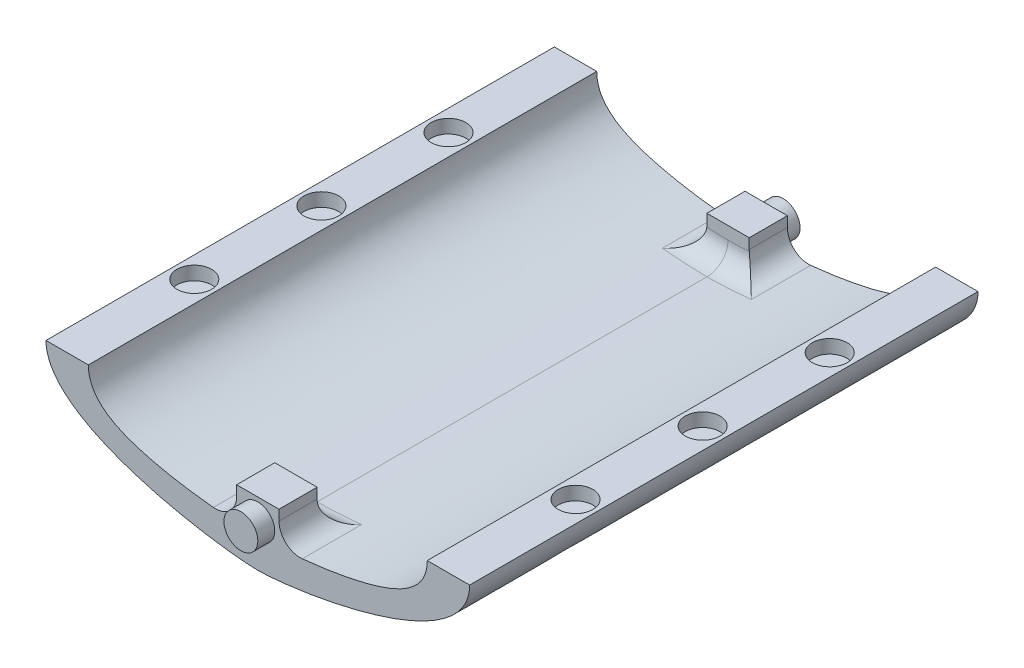
SolidWorks part; units mm, degrees
material "ASA-AERO"
ref_plane "Front Plane" through (0, 0, 0) normal (0, 0, 1) x (1, 0, 0)
ref_plane "Top Plane" through (0, 0, 0) normal (0, 1, 0) x (1, 0, 0)
ref_plane "Right Plane" through (0, 0, 0) normal (1, 0, 0) x (0, 0, -1)
sketch "Sketch2" plane through (0, 0, 0) normal (0, 0, 1) x (1, 0, 0)
  line L0 (0, 0) -> (0, 60.3008) construction
  line L1 (50, 0) -> (50, 60.3008) construction
  line L2 (0, 0) -> (25, 0) construction
  line L3 (0, -12) -> (0, -5)
  line L4 (25, -5) -> (25, -8) construction
  line L7 (25, 0) -> (25, -8) construction
  line L8 (50, 0) -> (50, 10) construction
  line L9 (50, 0) -> (112.8617, 0) construction
  line L10 (50, 10) -> (40, 10)
  line L11 (40, 10) -> (40, 19.3377) construction
  line L12 (25, 0) -> (25, -2) construction
  spline S0 degree 3 poles (0, -5) (3.5888, -5) (23.3364, -4.1199) (40, 2.9806) (40, 10) knots 0 0 0 0 0.567247 1 1 1 1
  spline S1 degree 3 poles (0, -12) (8.9645, -12) (50, -6.0901) (50, 10) knots 0 0 0 0 1 1 1 1
  point P4 (0, 0)
  point P8 (50, 0)
  dimension "D6" = 7
  dimension "D9" = 10
  dimension "D7" = 2
  dimension "D1" = 50
  dimension "D2" = 12
  dimension "D3" = 8
  dimension "D4" = 25
  dimension "D5" = 10
  dimension "D8" = 5
ref_plane "Plane1" through (0, 0, -30) normal (0, 0, 1) x (1, 0, 0)
sketch "Sketch3" plane through (0, 0, -30) normal (0, 0, 1) x (1, 0, 0)
  line L0 (0, 0) -> (0, 5) construction
  line L1 (0, 5) -> (30, 5) construction
  line L3 (0, 0) -> (0, -10) construction
  line L4 (0, -10) -> (0, -5)
  line L6 (15, 5) -> (15, -0.5) construction
  line L7 (15, -0.5) -> (15, -6) construction
  line L8 (30, 10) -> (30, 17.2192) construction
  line L9 (0, 5) -> (30, 5) construction
  line L10 (30, 10) -> (25.3573, 10)
  line L11 (30, 5) -> (30, 10) construction
  line L12 (25.3573, 10) -> (25.3573, 15.9682) construction
  spline S0 degree 3 poles (0, -5) (3.0165, -5) (13.9916, -1.9794) (25.3573, 5.259) (25.3573, 10) knots 0 0 0 0 0.540738 1 1 1 1
  spline S1 degree 3 poles (0, -10) (3.3297, -10) (17.9348, -6.1582) (30, 2.4303) (30, 10) knots 0 0 0 0 0.414466 1 1 1 1
  dimension "D1" = 5
  dimension "D2" = 30
  dimension "D3" = 5
  dimension "D4" = 10
  dimension "D5" = 5.5
  dimension "D6" = 5.5
ref_plane "Plane2" through (0, 0, -60) normal (0, 0, 1) x (1, 0, 0)
sketch "Sketch5" plane through (0, 0, -60) normal (0, 0, 1) x (1, 0, 0)
  line L0 (0, 0) -> (0, 10) construction
  line L1 (0, 10) -> (10, 10) construction
  line L2 (5, 10) -> (10, 10)
  line L3 (0, 0) -> (0, 5)
  line L4 (5, 10) -> (5, 13.8122) construction
  line L5 (10, 10) -> (10, 16.2533) construction
  line L6 (0, 0) -> (-6.3495, 0) construction
  line L7 (0, 5) -> (-5.8986, 5) construction
  spline S0 degree 3 poles (0, 5) (0.922, 5) (4.0789, 6.1641) (5, 8.7602) (5, 10) knots 0 0 0 0 0.511134 1 1 1 1
  spline S1 degree 3 poles (0, 0) (3.3679, 0) (8.0705, 2.1657) (10, 7.206) (10, 10) knots 0 0 0 0 0.525707 1 1 1 1
  dimension "D1" = 10
  dimension "D2" = 10
sketch "Sketch6" plane through (0, 0, 0) normal (1, 0, 0) x (0, 0, -1)
  spline S1 degree 2 poles (60, 0) (31.5145, -13.7022) (0, -12) knots 0 0 0 1 1 1
sketch "Sketch8" plane through (0, 0, 0) normal (1, 0, 0) x (0, 0, -1)
  spline S0 degree 2 poles (60, 5) (31.5811, -9.7434) (0, -5) knots 0 0 0 1 1 1
sketch3d "3DSketch3"
  spline S0 degree 2 poles (5, 10, -60) (26.7783, 10, -32.4788) (40, 10, 0) knots 0 0 0 1 1 1
  spline S1 degree 2 poles (10, 10, -60) (30, 10, -30) (50, 10, 0) knots 0 0 0 1 1 1
extrude "Boss-Extrude3" add sketch "Sketch2<6>" along normal blind 120 contours S0 L10 S1 L3
sketch "Sketch2<6>" plane through (0, 0, 0) normal (0, 0, 1) x (1, 0, 0) same geometry as "Sketch2"
mirror "Mirror3" about plane through (0, 0, 0) normal (1, 0, 0) of "Boss-Extrude3"
loft "Loft3" [suppressed] add profiles "Sketch2", "Sketch3", "Sketch5"
mirror "Mirror1" [suppressed] about plane through (0, 0, 0) normal (1, 0, 0) of bodies 103
sketch "Sketch11" [suppressed] plane through (0, 10, 0) normal (0, 1, 0) x (1, 0, 0)
  line L0 (-10, 60) -> (-5, 60) construction
  line L1 (-50, 0) -> (-43, 0) construction
  line L2 (-10, 60) -> (-50, 0) construction
  line L3 (-10, 60) -> (-5, 60)
  line L4 (-50, 0) -> (-43, 0)
  line L5 (-10, 60) -> (-50, 0)
  spline S0 degree 3 poles (1827.0171, 251.5153) (-147.7324, -878.8665) (-285.0351, 167.7557) (445.0771, 353.5106) (1502.103, 1374.1127) knots -15.336057 -15.336057 -15.336057 -15.336057 0.5 12.615004 12.615004 12.615004 12.615004 only from (-43, 0) to (-5, 60) construction
  spline S1 degree 3 poles (-43, 0) (-37.271, 10.4856) (-25.156, 31.0317) (-11.9308, 50.4759) (-5, 60) knots 0 0 0 0 0.5 1 1 1 1
extrude "Boss-Extrude2" [suppressed] add sketch "Sketch11" along normal blind 10
mirror "Mirror2" [suppressed] about plane through (0, 0, 0) normal (1, 0, 0) of bodies 104 105
sketch "Sketch13" plane through (0, 10, 0) normal (0, 1, 0) x (1, 0, 0)
  line L0 (-45, 0) -> (-45, -120) construction
  line L1 (-50, 0) -> (-40, 0)
  line L2 (-50, 0) -> (-50, -120)
  line L3 (-50, -120) -> (-40, -120)
  line L4 (-40, 0) -> (-40, -120)
  line L5 (-50, -120) -> (-40, -120) construction
  circle A0 centre (-45, -30) radius 4.1
  circle A1 centre (-45, -60) radius 4.1
  circle A2 centre (-45, -90) radius 4.1
  dimension "D1" = 8.2
  dimension "D2" = 8.2
  dimension "D3" = 8.2
  dimension "D4" = 30
  dimension "D5" = 30
  dimension "D6" = 30
  dimension "D7" = 10
extrude "Cut-Extrude3" cut sketch "Sketch13" against normal blind 3.2 contours A2 | A1 | A0
mirror "Mirror4" about plane through (0, 0, 0) normal (1, 0, 0) of "Cut-Extrude3"
sketch "Sketch14" plane through (0, 0, 120) normal (0, 0, 1) x (1, 0, 0)
  line L3 (-5, -7) -> (5, -7)
  line L4 (-5, -7) -> (-5, 3)
  line L5 (-5, 3) -> (5, 3)
  line L6 (5, -7) -> (5, 3)
  dimension "D1" = 10
  dimension "D2" = 10
  dimension "D3" = 5
  dimension "D5" = 3
extrude "Boss-Extrude4" add sketch "Sketch14" against normal blind 9 contours L4 L3 L6 L5
sketch "Sketch15" plane through (0, 0, 120) normal (0, 0, 1) x (1, 0, 0)
  line L1 (-5, 3) -> (5, -7) construction
  line L2 (-5, 3) -> (5, 3)
  line L3 (-5, 3) -> (-5, -7)
  line L4 (-5, -7) -> (5, -7)
  line L5 (5, 3) -> (5, -7)
  circle A1 centre (0, -2) radius 4
  dimension "D1" = 8
  dimension "D3" = 10
  dimension "D4" = 10
extrude "Boss-Extrude5" add sketch "Sketch15" along normal blind 4 contours A1
fillet "Fillet1" radius 5 4 edges at (5, -4.8278, 115.5) (-5, -4.8278, 115.5)
ref_plane "Plane3" through (0, 0, 60) normal (0, 0, -1) x (-1, 0, 0)
mirror "Mirror5" about plane through (0, 0, 60) normal (0, 0, -1) of "Fillet1", "Boss-Extrude4", "Boss-Extrude5"
